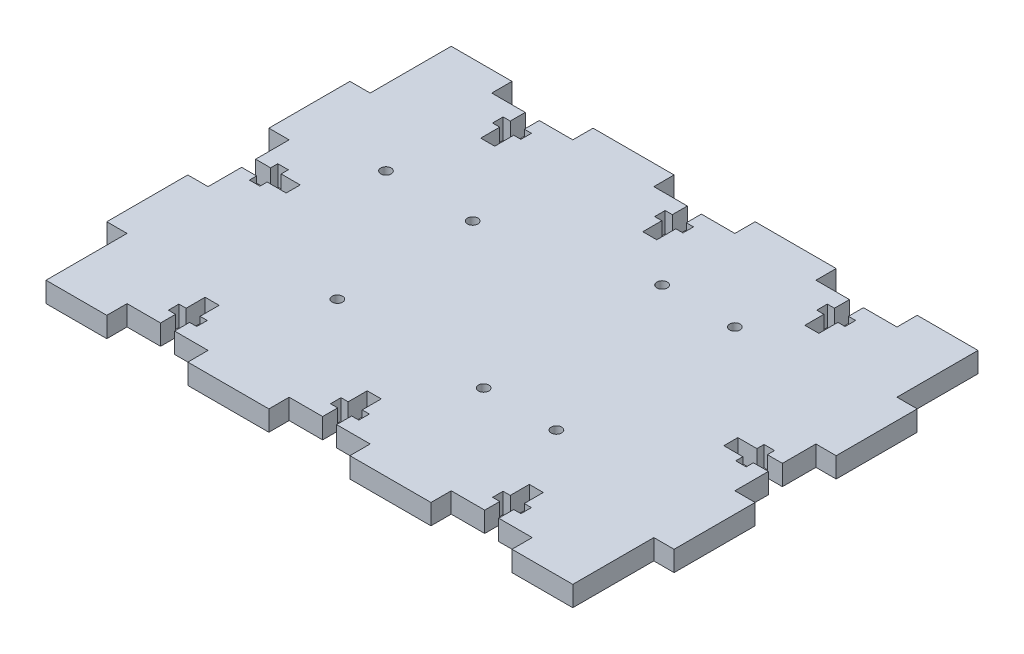
SolidWorks part; units mm, degrees
ref_plane "Front Plane" through (0, 0, 0) normal (0, 0, 1) x (1, 0, 0)
ref_plane "Top Plane" through (0, 0, 0) normal (0, 1, 0) x (1, 0, 0)
ref_plane "Right Plane" through (0, 0, 0) normal (1, 0, 0) x (0, 0, -1)
sketch "Sketch1" plane through (0, 0, 0) normal (0, 1, 0) x (1, 0, 0)
  line L1 (0, 0) -> (177.8, 0)
  line L2 (0, 0) -> (0, 127)
  line L3 (0, 127) -> (177.8, 127)
  line L4 (177.8, 0) -> (177.8, 127)
  dimension "D1" = 127
  dimension "D2" = 177.8
extrude "Boss-Extrude1" add sketch "Sketch1" along normal blind 6.35
sketch "Sketch2" plane through (0, 6.35, 0) normal (0, 1, 0) x (1, 0, 0)
  line L1 (0, 127) -> (6.35, 127)
  line L2 (0, 127) -> (0, 101.6)
  line L3 (0, 101.6) -> (6.35, 101.6)
  line L4 (6.35, 127) -> (6.35, 101.6)
  dimension "D1" = 25.4
  dimension "D2" = 6.35
extrude "Cut-Extrude1" cut sketch "Sketch2" against normal blind 6.35
pattern_linear "LPattern1" count 3 spacing 50.8 along (0, 0, 1) count 2 spacing 171.45 along (1, 0, 0) of "Cut-Extrude1"
sketch "Sketch3" plane through (0, 6.35, 0) normal (0, 1, 0) x (1, 0, 0)
  line L0 (6.35, 0) -> (171.45, 0) construction
  line L1 (25.4, 0) -> (50.8, 0)
  line L2 (25.4, 0) -> (25.4, 6.35)
  line L3 (25.4, 6.35) -> (50.8, 6.35)
  line L4 (50.8, 0) -> (50.8, 6.35)
  line L5 (0, 50.8) -> (0, 25.4) construction
  dimension "D1" = 25.4
  dimension "D2" = 6.35
  dimension "D3" = 25.4
extrude "Cut-Extrude2" cut sketch "Sketch3" against normal blind 6.35
pattern_linear "LPattern2" count 3 spacing 50.8 along (1, 0, 0) count 2 spacing 120.65 along (0, 0, -1) of "Cut-Extrude2"
ref_plane "Plane1" through (0, 0, -63.5) normal (0, 0, 1) x (1, 0, 0)
ref_plane "Plane2" through (88.9, 0, 0) normal (1, 0, 0) x (0, 0, -1)
sketch "Sketch4" plane through (0, 6.35, 0) normal (0, 1, 0) x (1, 0, 0)
  line L0 (171.45, 76.2) -> (171.45, 50.8) construction
  line L1 (171.45, 65.6971) -> (157.48, 65.6971)
  line L2 (171.45, 65.6971) -> (171.45, 61.3029)
  line L3 (171.45, 61.3029) -> (157.48, 61.3029)
  line L4 (157.48, 65.6971) -> (157.48, 61.3029)
  line L5 (177.8, 76.2) -> (171.45, 76.2) construction
  line L7 (163.449, 67.945) -> (166.751, 67.945)
  line L8 (163.449, 67.945) -> (163.449, 59.055)
  line L9 (163.449, 59.055) -> (166.751, 59.055)
  line L10 (166.751, 67.945) -> (166.751, 59.055)
  point P6 (171.45, 63.5)
  point P13 (165.1, 59.055)
  point P14 (166.751, 63.5)
  dimension "D1" = 13.97
  dimension "D2" = 4.3942
  dimension "D3" = 12.7
  dimension "D4" = 3.302
  dimension "D5" = 6.35
  dimension "D6" = 8.89
  dimension "D7" = 12.7
extrude "Cut-Extrude3" cut sketch "Sketch4" against normal blind 8.89 contours L1 L4 L3 L2 | L7 L10 L9 L8
mirror "Mirror1" about plane through (88.9, 0, 0) normal (1, 0, 0) of "Cut-Extrude3"
sketch "Sketch5" plane through (0, 6.35, 0) normal (0, 1, 0) x (1, 0, 0)
  line L0 (50.8, 6.35) -> (25.4, 6.35) construction
  line L1 (35.9029, 6.35) -> (40.2971, 6.35)
  line L2 (35.9029, 6.35) -> (35.9029, 20.32)
  line L3 (35.9029, 20.32) -> (40.2971, 20.32)
  line L4 (40.2971, 6.35) -> (40.2971, 20.32)
  line L5 (50.8, 0) -> (50.8, 6.35) construction
  line L6 (33.655, 14.351) -> (42.545, 14.351)
  line L7 (33.655, 14.351) -> (33.655, 11.049)
  line L8 (33.655, 11.049) -> (42.545, 11.049)
  line L9 (42.545, 14.351) -> (42.545, 11.049)
  point P6 (38.1, 20.32)
  point P12 (38.1, 11.049)
  point P15 (42.545, 12.7)
  dimension "D1" = 13.97
  dimension "D2" = 4.3942
  dimension "D3" = 12.7
  dimension "D4" = 3.302
  dimension "D5" = 8.89
  dimension "D6" = 12.7
  dimension "D7" = 6.35
extrude "Cut-Extrude4" cut sketch "Sketch5" against normal blind 30.48 contours L3 L4 L1 L2 | L7 L8 L9 L6
pattern_linear "LPattern3" count 3 spacing 50.8 along (1, 0, 0) of "Cut-Extrude4"
sketch "Sketch10" plane through (0, 6.35, 0) normal (0, 1, 0) x (1, 0, 0)
  line L1 (104.1908, 95.25) -> (127, 95.25)
  line L2 (104.1908, 95.25) -> (104.1908, 39.3192)
  line L3 (104.1908, 39.3192) -> (127, 39.3192)
  line L4 (127, 95.25) -> (127, 39.3192)
  line L5 (127, 120.65) -> (152.4, 120.65) construction
  line L6 (177.8, 76.2) -> (177.8, 101.6) construction
  dimension "D1" = 22.8092
  dimension "D2" = 55.9308
  dimension "D3" = 50.8
  dimension "D5" = 25.4
mirror "Mirror2" about plane through (0, 0, -63.5) normal (0, 0, 1) of "LPattern3"
hole_wizard "#4 Clearance Hole2" positions "Sketch12" profile "Sketch11" hole size "#4" standard "ANSI Inch"
sketch "Sketch12" plane through (0, 6.35, 0) normal (0, 1, 0) x (1, 0, 0)
  point P0 (104.1908, 95.25)
  point P3 (127, 95.25)
  point P6 (127, 39.3192)
  point P9 (104.1908, 39.3192)
sketch "Sketch11" plane through (104.1908, 6.35, -95.25) normal (1, 0, 0) x (0, 0, 1)
  line L0 (0, 0) -> (0, 11.1406)
  line L1 (0, 11.1406) -> (1.6319, 10.16)
  line L2 (1.6319, 10.16) -> (1.6319, 0)
  line L5 (1.6319, 0) -> (0, 0)
  line L10 (0, 11.1406) -> (-1.6319, 10.16) construction
  line L11 (0, -6.35) -> (0, 107.95) construction
  dimension "Hole Dia." = 3.2639
  dimension "Hole Depth" = 10.16
  dimension "Drill Angle" = 118
sketch "Sketch13" plane through (0, 6.35, 0) normal (0, 1, 0) x (1, 0, 0)
  line L0 (157.48, 65.6971) -> (157.48, 61.3029) construction
  line L1 (19.05, 90.551) -> (69.85, 90.551)
  line L2 (19.05, 90.551) -> (19.05, 36.449)
  line L3 (19.05, 36.449) -> (69.85, 36.449)
  line L4 (69.85, 90.551) -> (69.85, 36.449)
  line L5 (19.05, 90.551) -> (69.85, 36.449) construction
  line L6 (19.05, 36.449) -> (69.85, 90.551) construction
  line L8 (0, 101.6) -> (0, 76.2) construction
  point P0 (44.45, 63.5)
  point P7 (157.48, 63.5)
  point P8 (44.45, 90.551)
  dimension "D1" = 50.8
  dimension "D2" = 54.102
  dimension "D3" = 44.45
hole_wizard "#4 Clearance Hole3" positions "Sketch15" profile "Sketch14" hole size "#4" standard "ANSI Inch"
sketch "Sketch15" plane through (0, 6.35, 0) normal (0, 1, 0) x (1, 0, 0)
  line L0 (19.05, 90.551) -> (69.85, 90.551) construction
  line L3 (19.05, 90.551) -> (19.05, 36.449) construction
  point P0 (29.972, 82.931)
  point P2 (57.15, 82.931)
  point P4 (57.15, 40.513)
  dimension "D1" = 7.62
  dimension "D2" = 10.922
  dimension "D3" = 27.178
  dimension "D4" = 42.418
sketch "Sketch14" plane through (29.972, 6.35, -82.931) normal (1, 0, 0) x (0, 0, 1)
  line L0 (0, 0) -> (0, 11.1406)
  line L1 (0, 11.1406) -> (1.6319, 10.16)
  line L2 (1.6319, 10.16) -> (1.6319, 0)
  line L5 (1.6319, 0) -> (0, 0)
  line L10 (0, 11.1406) -> (-1.632, 10.16) construction
  line L11 (0, -6.35) -> (0, 107.95) construction
  dimension "Hole Dia." = 3.2639
  dimension "Hole Depth" = 10.16
  dimension "Drill Angle" = 118
